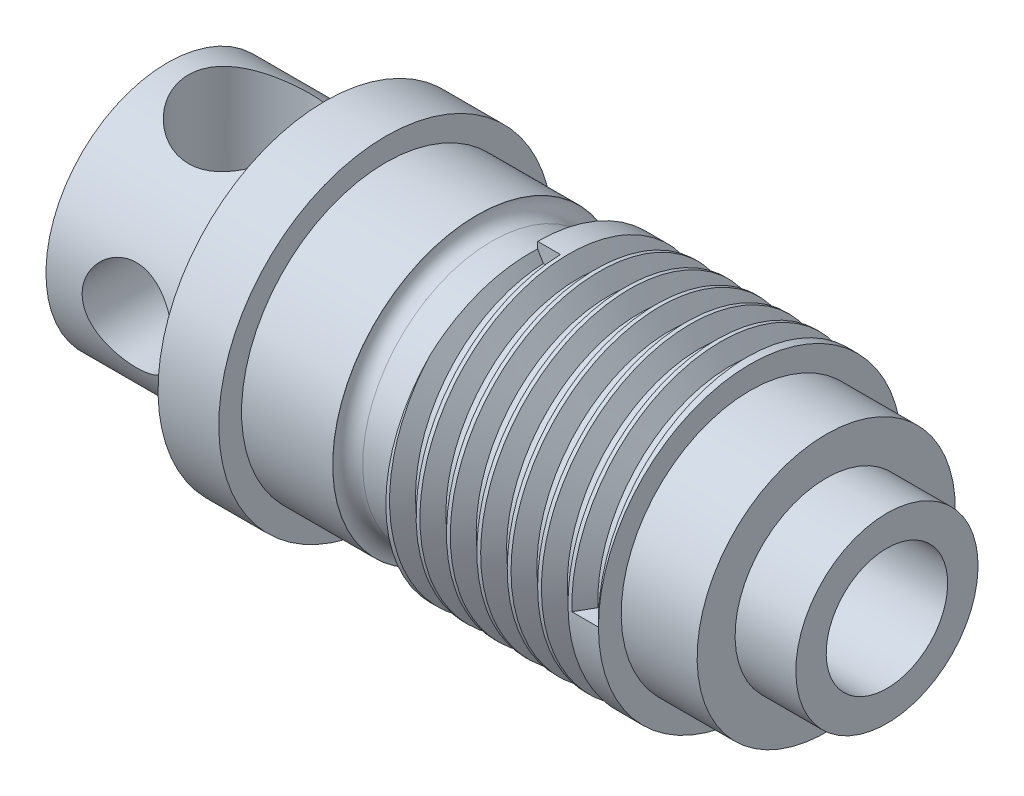
SolidWorks part; units mm, degrees
ref_plane "Спереди" through (0, 0, 0) normal (0, 0, 1) x (1, 0, 0)
ref_plane "Сверху" through (0, 0, 0) normal (0, 1, 0) x (1, 0, 0)
ref_plane "Справа" through (0, 0, 0) normal (1, 0, 0) x (0, 0, -1)
sketch "Эскиз1" plane through (0, 0, 0) normal (0, 0, 1) x (1, 0, 0)
  line L0 (13, 0) -> (-13, 0)
  line L1 (13, 0) -> (13, -3)
  line L2 (13, -3) -> (11, -3)
  line L3 (11, -3) -> (11, -4.25)
  line L4 (11, -4.25) -> (8.5, -4.25)
  line L5 (8.5, -4.25) -> (8.5, -5)
  line L6 (8.5, -5) -> (1.5, -5)
  line L7 (1.5, -5) -> (1.5, -4.75)
  line L8 (1, -4.25) -> (-0.01, -4.25)
  line L9 (-0.5, -4.74) -> (-0.5, -4.75)
  line L10 (-0.5, -4.75) -> (-3.5, -4.75)
  line L11 (-3.5, -4.75) -> (-3.5, -5.5)
  line L12 (-3.5, -5.5) -> (-5.5, -5.5)
  line L13 (-5.5, -5.5) -> (-5.5, -4)
  line L14 (-5.5, -4) -> (-10.6906, -4)
  line L15 (-10.6906, -4) -> (-13, 0)
  arc A0 (1.5, -4.75) -> (1, -4.25) centre (1, -4.75) ccw
  arc A1 (-0.01, -4.25) -> (-0.5, -4.74) centre (-0.01, -4.74) ccw
  point P3 (0, 0)
  point P20 (1.5, -4.25)
  point P23 (-0.5, -4.25)
  dimension "D15" = 0.5
  dimension "D16" = 0.49
  dimension "D1" = 26
  dimension "D2" = 3
  dimension "D3" = 2
  dimension "D4" = 4.25
  dimension "D5" = 4.5
  dimension "D6" = 5
  dimension "D7" = 7
  dimension "D8" = 2
  dimension "D9" = 4.75
  dimension "D10" = 3
  dimension "D11" = 5.5
  dimension "D12" = 2
  dimension "D13" = 60
  dimension "D14" = 4
revolve "Повернуть1" add sketch "Эскиз1" angle 360 about L0
sketch "Эскиз2" plane through (0, 0, 0) normal (0, 0, 1) x (1, 0, 0)
  line L0 (-5.5, 4) -> (-5.5, -4) construction
  circle A0 centre (-8, 0) radius 1.5
  dimension "D2" = 3
  dimension "D1" = 2.5
extrude "Вырез-Вытянуть1" cut sketch "Эскиз2" against normal through all both and the other way through all
sketch "Эскиз3" plane through (0, 0, 0) normal (0, 1, 0) x (1, 0, 0)
  line L0 (-5.5, 4) -> (-5.5, -4) construction
  circle A0 centre (-8, 0) radius 2
  dimension "D1" = 2.5
  dimension "D2" = 4
extrude "Вырез-Вытянуть2" cut sketch "Эскиз3" against normal through all both and the other way through all
thread "Резьба1" pitch 1 method cut profile "Профиль резьбы1" start angle 0, offset 0, length 6.25, pitch 1, diameter 10
ref_plane "Плоскость1" through (8.5, 0, 5) normal (0, -1, 0) x (0, 0, 1)
sketch "Профиль резьбы1" plane through (8.5, 0, 5) normal (0, -1, 0) x (0, 0, 1)
  line L0 (0, 0) -> (0, 1) construction
  line L11 (0, 0) -> (0, 0.875)
  line L12 (0, 0.875) -> (-0.5413, 0.5625)
  line L13 (-0.5413, 0.5625) -> (-0.5413, 0.3125)
  line L15 (-0.5413, 0.3125) -> (0, 0)
  line L17 (-0.5413, 0.4375) -> (0, 0.4375) construction
  point P2 (0, 0)
  dimension "Pitch" = 1
  dimension "Profile_Angle" = 60
  dimension "Profile_Land" = 0.25
  dimension "Profile_Height" = 0.5413
sketch "Эскиз6" plane through (13, 0, 0) normal (1, 0, 0) x (0, 0, -1)
  circle A0 centre (0, 0) radius 2
  dimension "D1" = 4
extrude "Вырез-Вытянуть3" cut sketch "Эскиз6" against normal blind 21
